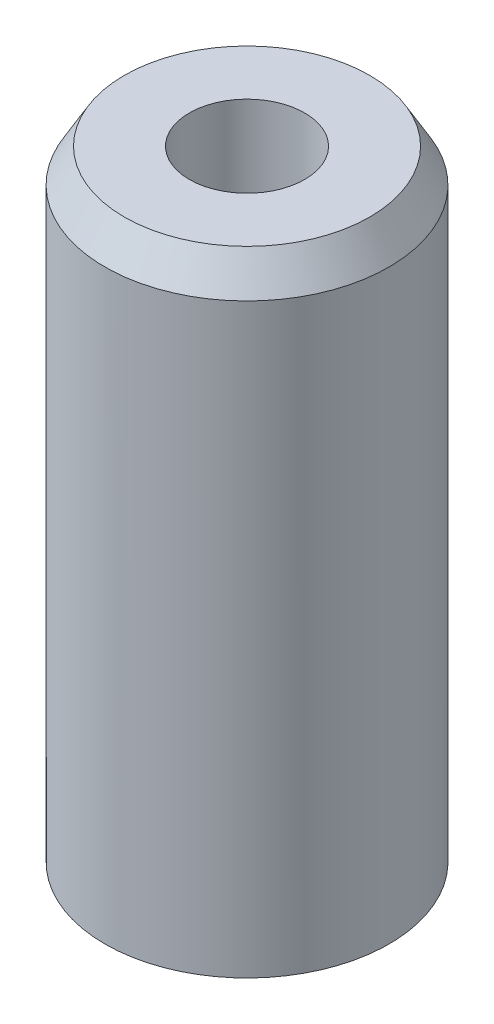
SolidWorks part; units mm, degrees
ref_plane "Front Plane" through (0, 0, 0) normal (0, 0, 1) x (1, 0, 0)
ref_plane "Top Plane" through (0, 0, 0) normal (0, 1, 0) x (1, 0, 0)
ref_plane "Right Plane" through (0, 0, 0) normal (1, 0, 0) x (0, 0, -1)
sketch "Sketch1" plane through (0, 0, 0) normal (0, 1, 0) x (1, 0, 0)
  circle A0 centre (0, 0) radius 15
  dimension "SHAFT_OD" = 30
extrude "Boss-Extrude1" add sketch "Sketch1" along normal blind 67.4816
sketch "Sketch2" plane through (0, 0, 0) normal (0, 1, 0) x (1, 0, 0)
  circle A0 centre (0, 0) radius 6.0876
  dimension "BORE_D" = 12.1752
extrude "Cut-Extrude1" cut sketch "Sketch2" along normal through all
chamfer "Chamfer1" distance 3.5443 angle 30 2 edges at (0, 67.4816, 15) (0, 0, 15) first distance on face at (0, 67.4816, 15) first distance on face at (0, 0, 6.0876)
